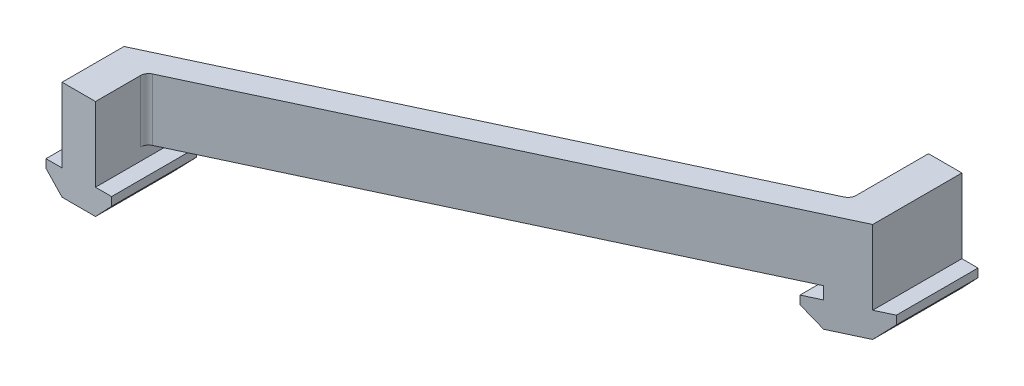
SolidWorks part; units mm, degrees
note: The reader was unsure of these and kept them because the rebuilt part matched: shared geometry of "Sketch2<4>".
ref_plane "Front Plane" through (0, 0, 0) normal (0, 0, 1) x (1, 0, 0)
ref_plane "Top Plane" through (0, 0, 0) normal (0, 1, 0) x (1, 0, 0)
ref_plane "Right Plane" through (0, 0, 0) normal (1, 0, 0) x (0, 0, -1)
sketch "Sketch1" plane through (0, 0, 0) normal (0, 0, 1) x (1, 0, 0)
  line L3 (0, 0) -> (0, 9.1103) construction
  line L8 (-4.05, 18) -> (4.05, 18)
  line L14 (4.05, 18) -> (4.05, 0)
  line L15 (-4.05, 18) -> (-4.05, 0)
  line L16 (-4.05, 18) -> (-115.95, 18)
  line L17 (-60, 18) -> (-60, 3) construction
  line L18 (-115.95, 3) -> (-4.05, 3)
  line L19 (-115.95, 18) -> (-124.05, 18)
  line L20 (-115.95, 18) -> (-115.95, 0)
  line L21 (-124.05, 18) -> (-124.05, 0)
  line L29 (-124.05, 0) -> (-115.95, 0)
  point P4 (0, 0)
  line B0 (7.95, 0) -> (7.95, -2.04)
  line B1 (4.048, -6.1524) -> (-4.048, -6.1524)
  line B2 (-7.95, -2.04) -> (-7.95, 0)
  line B3 (-7.95, 0) -> (7.95, 0)
  line B4 (7.95, -2.04) -> (4.048, -6.1524)
  line B5 (-4.048, -6.1524) -> (-7.95, -2.04)
  line B6 (4.05, 0) -> (-4.05, 0) construction
  line B7 (-112.05, 0) -> (-112.05, -2.04)
  line B8 (-115.952, -6.1524) -> (-124.048, -6.1524)
  line B9 (-127.95, -2.04) -> (-127.95, 0)
  line B10 (-127.95, 0) -> (-112.05, 0)
  line B11 (-112.05, -2.04) -> (-115.952, -6.1524)
  line B12 (-124.048, -6.1524) -> (-127.95, -2.04)
  line B13 (-115.95, 0) -> (-124.05, 0) construction
  dimension "D1" = 120
  dimension "D2" = 3
  dimension "D7" = 60
  dimension "D8" = 15
sketch_block_instance "Extrusion Profile-4"
sketch_block "Extrusion Profile" parameters "D1"=8.44, "D2"=2.6, "D3"=6, "D4"=16.7, "D6"=5.6686, "D7"=2.0404, "D8"=8.0963, "D9"=15.9, "D5"=2.4157
sketch_block_instance "Extrusion Profile-5"
extrude "Boss-Extrude1" add sketch "Sketch1" along normal blind 60
sketch "Sketch2" plane through (0, 18, 0) normal (0, 1, 0) x (1, 0, 0)
  line L0 (4.05, 0) -> (-128.5779, -62.1208)
  line L2 (11.1229, -3.3127) -> (-126.033, -67.5543)
  line L5 (-126.033, -67.5543) -> (-83.6167, -158.113)
  line L6 (-83.6167, -158.113) -> (53.5391, -93.8713)
  line L7 (53.5391, -93.8713) -> (11.1229, -3.3127)
  line L8 (-128.5779, -62.1208) -> (-170.9941, 28.4378)
  line L9 (-170.9941, 28.4378) -> (-38.3662, 90.5586)
  line L10 (-38.3662, 90.5586) -> (4.05, 0)
  line L11 (8.5779, 2.1208) -> (-128.5779, -62.1208) construction
  line L12 (-128.5779, -62.1208) -> (-124.05, -60)
  dimension "D3" = 100
  dimension "D4" = 5
  dimension "D1" = 6
  dimension "D2" = 100
  dimension "D5" = 5
extrude "Cut-Extrude2" cut sketch "Sketch2" against normal through all
sketch "Sketch3" plane through (0, 0, 60) normal (0, 0, 1) x (1, 0, 0)
  line L11 (-124.05, 18) -> (-124.05, 0)
  line L12 (-124.05, 0) -> (-127.95, 0)
  line L13 (-127.95, 0) -> (-127.95, -2.04)
  line L14 (-127.95, -2.04) -> (-124.048, -6.1524)
  line L15 (-124.048, -6.1524) -> (-115.952, -6.1524)
  line L16 (-115.952, -6.1524) -> (-112.05, -2.04)
  line L17 (-112.05, -2.04) -> (-112.05, 0)
  line L18 (-112.05, 0) -> (-115.95, 0)
  line L19 (-115.95, 0) -> (-115.95, 3)
  line L20 (-115.95, 3) -> (-115.95, 18)
  line L21 (-115.95, 18) -> (-124.05, 18)
extrude "Boss-Extrude2" add sketch "Sketch3" along normal mid plane 30
extrude "Cut-Extrude3" cut sketch "Sketch2<4>" against normal through all contours L8 L9 L10 L0
sketch "Sketch2<4>" plane through (0, 18, 0) normal (0, 1, 0) x (1, 0, 0) same geometry as "Sketch2"
sketch "Sketch4" plane through (0, 18, 0) normal (0, 1, 0) x (1, 0, 0)
  line L0 (-109.9045, -60) -> (-115.95, -62.8316)
  line L1 (-115.95, -75) -> (-115.95, -56.2061) construction
  line L2 (4.05, -6.6255) -> (-109.9045, -60) construction
  line L3 (-109.9045, -60) -> (-115.95, -60)
  line L4 (-115.95, -60) -> (-115.95, -62.8316)
extrude "Boss-Extrude3" add sketch "Sketch4" against normal up to surface (15 mm away) up to face at (-69.9809, 3, 38.0839)
sketch "Sketch6" plane through (0, 0, 0) normal (0, 0, -1) x (-1, 0, 0)
  line L0 (-4.05, 0) -> (-7.95, 0)
  line L1 (-7.95, 0) -> (-7.95, -2.04)
  line L2 (-7.95, -2.04) -> (-4.05, -6.1503)
  line L3 (-4.05, -6.1503) -> (4.048, -6.1524)
  line L4 (4.048, -6.1524) -> (7.95, -2.04)
  line L5 (7.95, -2.04) -> (7.95, 0)
  line L6 (7.95, 0) -> (4.05, 0)
  line L7 (4.05, 0) -> (4.05, 3)
  line L8 (4.05, 3) -> (4.05, 18)
  line L9 (-4.05, 18) -> (124.05, 18) construction
  line L10 (4.05, 18) -> (-4.05, 18)
  line L11 (-4.05, 18) -> (-4.05, 0)
extrude "Boss-Extrude4" add sketch "Sketch6" along normal mid plane 30
sketch "Sketch7" plane through (0, 18, 0) normal (0, 1, 0) x (1, 0, 0)
  line L6 (-4.05, -10.4195) -> (-115.95, -62.8316) construction
  line L7 (-7.95, -15) -> (-7.95, 15) construction
  line L8 (-7.95, -12.2462) -> (-7.95, -15)
  line L9 (-7.95, -15) -> (7.95, -15)
  line L10 (7.95, -15) -> (7.95, -4.7988)
  line L11 (7.95, -15) -> (7.95, 15) construction
  line L12 (7.95, -4.7988) -> (-7.95, -12.2462)
extrude "Cut-Extrude4" cut sketch "Sketch7" against normal through all
fillet "Fillet1" radius 2 2 edges at (-4.05, 10.5, 3.7939) (-115.95, 10.5, 62.8316)
